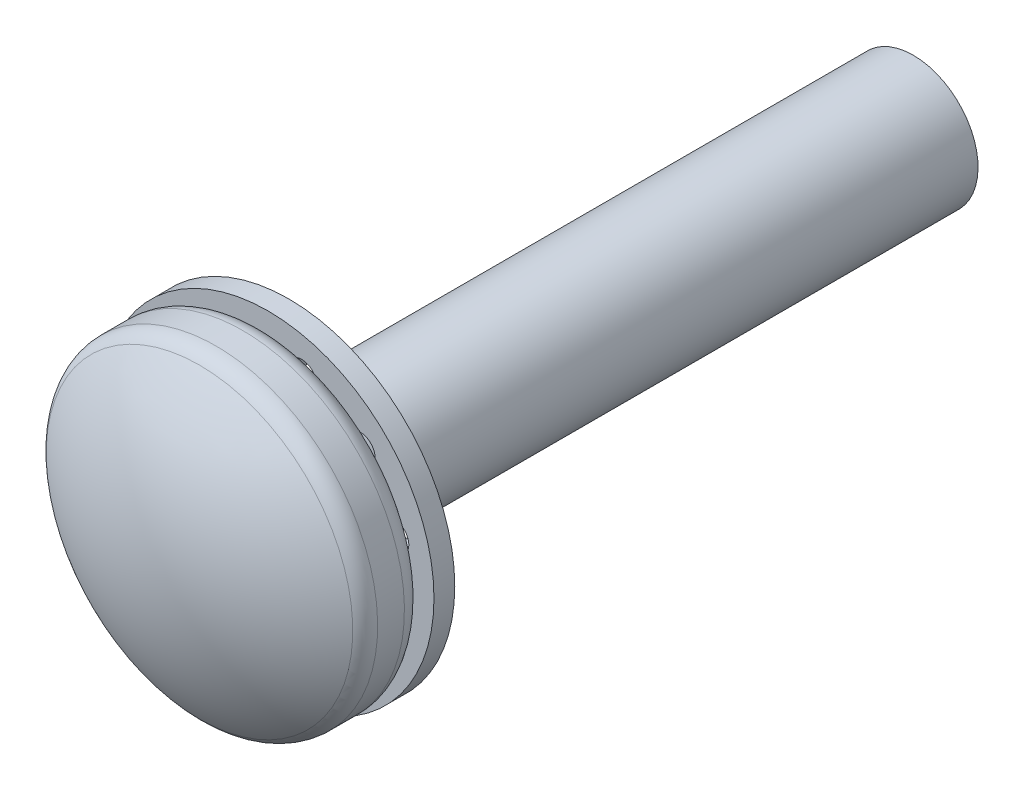
SolidWorks part; units mm, degrees
material "AISI 304"
ref_plane "Front Plane" through (0, 0, 0) normal (0, 0, 1) x (1, 0, 0)
ref_plane "Top Plane" through (0, 0, 0) normal (0, 1, 0) x (1, 0, 0)
ref_plane "Right Plane" through (0, 0, 0) normal (1, 0, 0) x (0, 0, -1)
sketch "Sketch1" plane through (0, 0, 0) normal (0, 0, 1) x (1, 0, 0)
  circle A0 centre (0, 0) radius 2.413
  dimension "decimal equ" = 4.826
curve "Helix/Spiral1" pitch 0.7937 height 19.8438 turns 25 parameters "helix length"=19.8438, "pitch"=0.7937
sketch "Sketch2" plane through (0, 0, 0) normal (1, 0, 0) x (0, 0, -1)
  line L0 (0.2977, 2.413) -> (0.3969, 2.413)
  line L1 (0.3969, 2.413) -> (0.6945, 1.8974)
  line L2 (0.2977, 2.413) -> (0, 1.8974)
  line L3 (0, 1.8974) -> (0.6945, 1.8974)
  line L4 (0, 1.8974) -> (0, 2.413) construction
  line L5 (0, 2.413) -> (0, -2.413) construction
  line L6 (0.1488, 2.1552) -> (0.5457, 2.1552) construction
  line L7 (0, 2.413) -> (0, -2.413) construction
  line L8 (0.3473, 2.413) -> (0.3473, 1.8974) construction
  point P6 (-3.175, -2.413)
  dimension "D1" = 60
  dimension "D3" = 0.0992
  dimension "D4" = 0.3969
  dimension "D2" = 3.175
sketch "Sketch3" plane through (0, 0, 0) normal (1, 0, 0) x (0, 0, -1)
  line L0 (0, 0) -> (-19.05, 0) construction
  line L1 (0, 1.8974) -> (0.6945, 1.8974) construction
  line L2 (0, 0) -> (-19.05, 0)
  line L3 (0, 0) -> (0, 1.8974)
  line L4 (0, 1.8974) -> (-19.05, 1.8974)
  line L5 (-19.05, 0) -> (-19.05, 1.8974)
  dimension "length" = 19.05
revolve "Revolve1" add sketch "Sketch3" angle 360 about L0
sweep "Sweep1" [suppressed] add profiles "Sketch2" path "Helix/Spiral1"
sketch "Sketch33" [suppressed] plane through (0, 0, 0) normal (0, 0, -1) x (-1, 0, 0)
  circle A1 centre (0, 0) radius 2.413
extrude "Extrude6" [suppressed] cut sketch "Sketch33" along normal through all
sketch "Sketch34" [suppressed] plane through (0, 0, 0) normal (0, 0, -1) x (-1, 0, 0)
  circle A0 centre (0, 0) radius 1.8974 construction
  circle A1 centre (0, 0) radius 1.8026
  dimension "D2" = 3.6051
extrude "Extrude7" [suppressed] cut sketch "Sketch34" against normal through all draft 45 flip side to cut
sketch "Sketch10" plane through (0, 0, 0) normal (1, 0, 0) x (0, 0, -1)
  line L0 (0, 0) -> (23.0169, 0) construction
  line L1 (-273.05, 12.7) -> (-19.05, 12.7)
  line L2 (-273.05, 12.7) -> (-273.05, 0)
  line L3 (-273.05, 0) -> (-19.05, 0)
  line L4 (-19.05, 12.7) -> (-19.05, 0)
  line L5 (-19.05, 0) -> (-19.05, 1.8974) construction
  dimension "D1" = 254
  dimension "D2" = 12.7
revolve "Cut-Revolve2" [suppressed] cut sketch "Sketch10" angle 360 about L0
sketch "Sketch35" plane through (0, 0, 0) normal (1, 0, 0) x (0, 0, -1)
  line L0 (-19.05, 2.413) -> (-19.05, 1.8974)
  line L1 (-19.05, 1.8974) -> (-18.1356, 1.8974)
  line L2 (-18.1356, 1.8974) -> (-17.62, 2.413)
  line L3 (-19.05, 2.413) -> (-17.62, 2.413)
  dimension "D1" = 45
  dimension "D2" = 0.9144
revolve "Cut-Revolve4" [suppressed] cut sketch "Sketch35" angle 360 about L2
sketch "Sketch8" plane through (0, 0, 0) normal (1, 0, 0) x (0, 0, -1)
  line L0 (0, 0) -> (-6.2449, 0) construction
  line L1 (-22.4282, 0) -> (-19.05, 0)
  line L2 (-22.4282, 0) -> (-22.4282, 4.7371)
  line L3 (-22.4282, 4.7371) -> (-19.05, 4.7371)
  line L4 (-19.05, 0) -> (-19.05, 4.7371)
  line L5 (-22.4282, -4.7371) -> (-19.05, -4.7371) construction
  line L6 (-19.05, 0) -> (-19.05, 1.8974) construction
  dimension "head dia" = 9.4742
  dimension "head height" = 3.3782
revolve "Revolve2" add sketch "Sketch8" angle 360 about L0
sketch "Sketch11" plane through (0, 0, 0) normal (1, 0, 0) x (0, 0, -1)
  line L0 (-20.7391, 4.7371) -> (-20.7391, -4.0894) construction
  line L1 (-22.4282, 0) -> (-6.8951, 0) construction
  line L2 (-22.4282, 4.7371) -> (-19.05, 4.7371) construction
  line L3 (-22.4282, 0) -> (-22.4282, 4.7371) construction
  line L4 (-20.4431, 4.7371) -> (-19.6581, 4.7371)
  line L6 (-19.05, 0) -> (-19.05, 4.7371) construction
  line L7 (-19.05, 4.129) -> (-18.415, 4.129)
  line L8 (-18.415, 4.129) -> (-18.415, 5.3721)
  line L9 (-18.415, 5.3721) -> (-23.0632, 5.3721)
  line L10 (-23.0632, 5.3721) -> (-23.0632, 0)
  line L11 (-23.0632, 0) -> (-22.4282, 0)
  arc A0 (-20.9295, 4.494) -> (-22.4282, 0) centre (-14.941, 0) ccw
  arc A1 (-19.05, 4.129) -> (-19.6581, 4.7371) centre (-19.6581, 4.129) ccw
  arc A2 (-20.9295, 4.494) -> (-20.4431, 4.7371) centre (-20.4431, 4.129) cw
  dimension "D1" = 0.6081
  dimension "D2" = 0.635
  dimension "D3" = 0.635
  dimension "D4" = 0.635
revolve "Cut-Revolve3" cut sketch "Sketch11" angle 360 about L1
ref_plane "Plane1" through (0, 0, 22.4282) normal (0, 0, 1) x (1, 0, 0)
sketch "Sketch12" plane through (0, 0, 22.4282) normal (0, 0, 1) x (1, 0, 0)
  line L0 (0.508, 2.3264) -> (0.508, 1.1906)
  line L1 (0.508, 1.1906) -> (1.1906, 0.508) construction
  line L2 (1.1906, 0.508) -> (2.3264, 0.508)
  line L3 (0, 2.3813) -> (0, 0)
  line L4 (0, 0) -> (2.3813, 0)
  line L5 (0, 0) -> (0, 4.7371) construction
  line L6 (0, 0) -> (0.8493, 0.8493) construction
  line L7 (1.1906, 0) -> (1.1906, 1.5633) construction
  line L8 (0.508, 1.1906) -> (0.7079, 0.7079)
  line L9 (1.1906, 0.508) -> (0.7079, 0.7079)
  line L10 (0, 0) -> (0, -1.0114) construction
  line L11 (-0.508, 2.3264) -> (-0.508, 1.1906) construction
  arc A0 (2.3813, 0) -> (2.3264, 0.508) centre (0, 0) ccw
  arc A1 (0.508, 2.3264) -> (0, 2.3813) centre (0, 0) ccw
  arc A2 (-2.3813, 0) -> (-2.3264, 0.508) centre (0, 0) cw construction
  dimension "phillips dia" = 4.7625
  dimension "D2" = 45
  dimension "D4" = 22.5
  dimension "slot width" = 1.016
extrude "Cut-Extrude1" [suppressed] cut sketch "Sketch12" against normal blind 2.8715
draft "Draft3" [suppressed] type of draft neutral plane draft angle 15 neutral plane "Plane1" faces to draft 2 parameters "D1"=15
draft "Draft4" [suppressed] type of draft neutral plane draft angle 5 neutral plane "Plane1" faces to draft 4 parameters "D1"=5
pattern_circular "CirPattern1" [suppressed] count 4 over 360 about axis through (0, 0, 22.4282) along (0, 0, -1) of bodies 110
ref_plane "Plane8" through (0, 0, 18.9187) normal (0, 0, -1) x (-1, 0, 0)
sketch "Sketch18" plane through (0, 0, 18.9187) normal (0, 0, 1) x (1, 0, 0)
  line L0 (0, -1.8974) -> (0, -4.8641) construction
  circle A0 centre (0, 0) radius 4.8641
  circle A1 centre (0, 0) radius 1.8974 construction
  circle A3 centre (0, 0) radius 3.3808
  point P10 (0, -3.3808)
  dimension "washer dia." = 9.7282
  dimension "D1" = 2.9667
  dimension "D2" = 1.4833
extrude "Extrude1" add sketch "Sketch18" against normal blind 0.6096 separate body
sketch "Sketch19" plane through (0, 0, 18.3091) normal (0, 0, -1) x (-1, 0, 0)
  line L0 (0, 0) -> (0, 8.8432) construction
  line L1 (1.3953, 3.5272) -> (0, 0)
  line L2 (0.9883, 3.6882) -> (0, 0) construction
  line L3 (0.5552, 3.7523) -> (0, 0)
  line L4 (0.4948, 3.3444) -> (1.2436, 3.1437) construction
  arc A0 (1.3953, 3.5272) -> (0.5552, 3.7523) centre (0.9883, 3.6882) ccw
  circle A1 centre (0, 0) radius 3.3808 construction
  circle A5 centre (0, 0) radius 4.2561
  circle A6 centre (0, 0) radius 4.2561 construction
  dimension "D2" = 0.8755
  dimension "D3" = 15
extrude "Cut-Extrude2" cut sketch "Sketch19" against normal through all
pattern_circular "CirPattern2" count 12 over 360 of "Cut-Extrude2"
ref_plane "Plane6" through (0, 3.3444, 0) normal (0, 1, 0) x (-1, 0, 0)
sketch "Sketch25" plane through (0, 3.3444, 0) normal (0, 1, 0) x (-1, 0, 0)
  line L2 (-0.4948, 18.6139) -> (0.4948, 18.6139) construction
  line L4 (-0.4948, 18.3091) -> (0.4948, 18.3091)
  line L5 (-0.4948, 18.3091) -> (-0.4948, 18.9187)
  line L6 (-0.4948, 18.9187) -> (0.4948, 18.9187)
  line L7 (0.4948, 18.3091) -> (0.4948, 18.9187)
  line L14 (0, 18.6139) -> (0, 18.3091) construction
ref_plane "Plane7" through (0, 1.8974, 0) normal (0, 1, 0) x (-1, 0, 0)
sketch "Sketch26" plane through (0, 1.8974, 0) normal (0, 1, 0) x (-1, 0, 0)
  line L0 (-0.4781, 18.4931) -> (-0.2301, 19.05)
  line L1 (-0.4781, 18.4931) -> (0.2301, 18.1778)
  line L2 (-0.2301, 19.05) -> (0.4781, 18.7347)
  line L3 (0.2301, 18.1778) -> (0.4781, 18.7347)
  line L7 (-0.3541, 18.7716) -> (0.3541, 18.4562) construction
  line L8 (-0.124, 18.3354) -> (0, 18.6139) construction
  line L9 (-0.2301, 19.05) -> (-0.2301, 18.9187) construction
  line L11 (4.8641, 18.9187) -> (-4.8641, 18.9187) construction
  line L13 (0.4781, 18.9187) -> (-0.2301, 18.9187) construction
  line L14 (-0.4948, 18.3091) -> (-0.4948, 18.9187) construction
  line L15 (-0.4948, 18.6139) -> (0.4948, 18.6139) construction
  dimension "D1" = 0.7752
  dimension "D3" = 24
loft "Loft4" add profiles "Sketch25", "Sketch26" connector at (-0.4948, 3.3444, 18.9187) connector at (-0.4781, 1.8974, 18.7347)
sketch "Sketch30" plane through (0, 3.3444, 0) normal (0, 1, 0) x (-1, 0, 0)
  line L4 (-0.4948, 18.3091) -> (0.4948, 18.3091)
  line L5 (-0.4948, 18.3091) -> (0.4948, 18.3091)
  line L6 (0.4948, 18.3091) -> (0.4948, 18.9187)
  line L7 (0.4948, 18.3091) -> (0.4948, 18.9187)
  line L8 (0.4948, 18.9187) -> (-0.4948, 18.9187)
  line L9 (0.4948, 18.9187) -> (-0.4948, 18.9187)
  line L10 (-0.4948, 18.9187) -> (-0.4948, 18.3091)
  line L11 (-0.4948, 18.9187) -> (-0.4948, 18.3091)
  dimension "D1" = 0
extrude "Extrude5" add sketch "Sketch30" along normal blind 0.0508 separate body
pattern_circular "CirPattern8" count 12 over 360 of bodies 182 144
combine bodies "Combine2" operation type add bodies to combine 144 182 187 188 189 190 191 192 193 194 195 196 197 198 199 200 201 202 203 204 205 206 207 208 120
equation "\"D3@Sketch2\" = \"pitch@Helix/Spiral1\"*.125"
equation "\"D4@Sketch2\" = \"pitch@Helix/Spiral1\"*.5"
equation "\"D1@Sketch11\" = \"head height@Sketch8\"*.18"
equation "\"D1@Cut-Extrude1\" = \"head height@Sketch8\"*.85"
equation "\"D2@Sketch19\" = \"washer dia.@Sketch18\"*.09"
equation "\"D1@Sketch19\" = \"washer dia.@Sketch18\"*.0625"
equation "\"helix length@Helix/Spiral1\" = \"length@Sketch3\" + \"pitch@Helix/Spiral1\""
equation "\"D2@Sketch34\" = \"D1@Sketch34\"*.95"
equation "\"D1@Plane8\" = \"D2@Sketch26\""
equation "\"D2@Sketch2\" = \"pitch@Helix/Spiral1\"*4"
equation "\"D2@Sketch35\" = \"washer width@Extrude1\"*1.5"
equation "\"D2@Sketch18\" = \"D1@Sketch18\"/2"
equation "\"D1@Sketch26\" = \"D4@Sketch19\""
